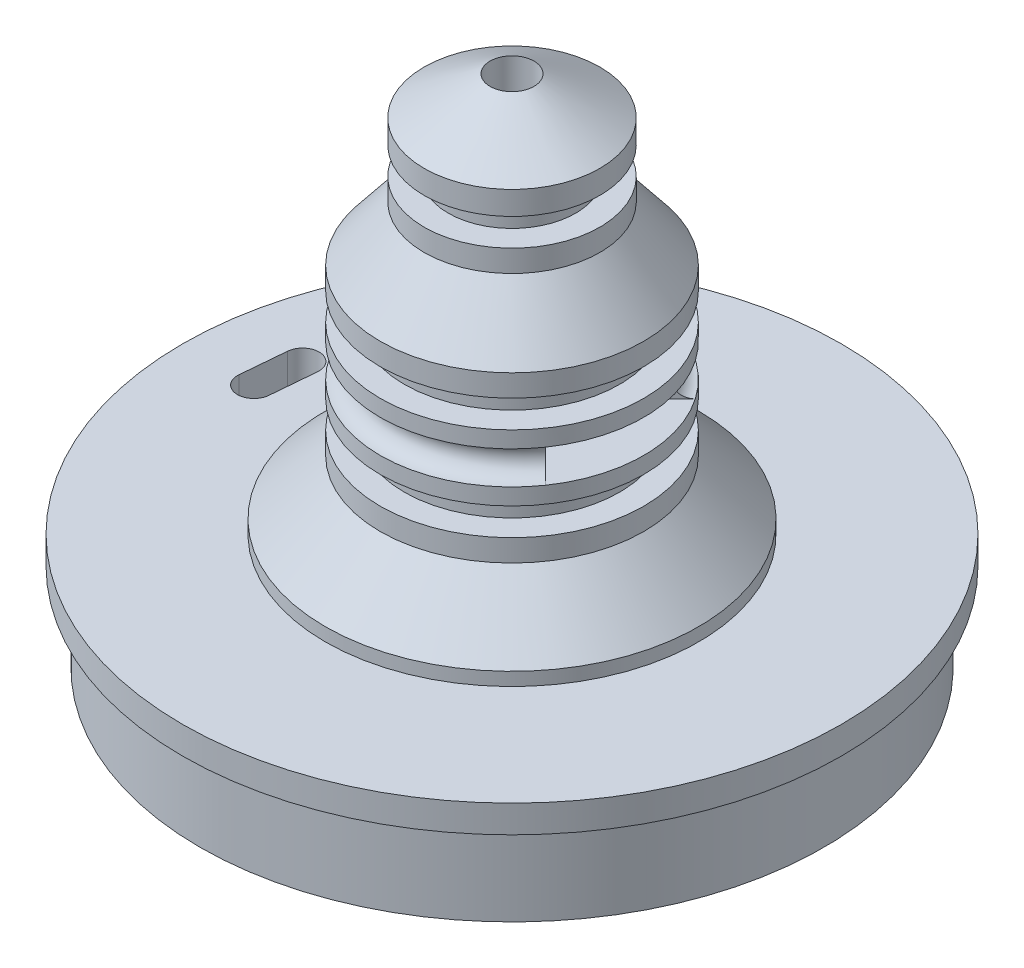
SolidWorks part; units mm, degrees
ref_plane "Спереди" through (0, 0, 0) normal (0, 0, 1) x (1, 0, 0)
ref_plane "Сверху" through (0, 0, 0) normal (0, 1, 0) x (1, 0, 0)
ref_plane "Справа" through (0, 0, 0) normal (1, 0, 0) x (0, 0, -1)
sketch "Эскиз1" plane through (0, 0, 0) normal (0, 0, 1) x (1, 0, 0)
  line L0 (0, 0) -> (0, 60) construction
  line L1 (17, 27) -> (17, 25.8)
  line L2 (2, 62.0979) -> (2, 15.3)
  line L6 (8, 56.5) -> (5.8, 56.5)
  line L7 (5.8, 56.5) -> (5.8, 54)
  line L8 (5.8, 54) -> (8, 54)
  line L10 (8, 58.6338) -> (8, 56.5)
  line L11 (8, 54) -> (8, 52)
  line L12 (8, 52) -> (12, 47)
  line L13 (12, 47) -> (12, 45)
  line L14 (12, 45) -> (9.8, 45)
  line L15 (9.8, 45) -> (9.8, 42.5)
  line L16 (9.8, 42.5) -> (12, 42.5)
  line L17 (12, 39.5) -> (9.0242, 39.5) construction
  line L18 (12, 42.5) -> (12, 41)
  line L19 (12, 36.5) -> (12, 38)
  line L20 (12, 34) -> (9.8, 34)
  line L21 (9.8, 34) -> (9.8, 36.5)
  line L22 (9.8, 36.5) -> (12, 36.5)
  line L23 (12, 34) -> (12, 32)
  line L24 (12, 32) -> (17, 27)
  line L29 (17, 25.8) -> (30, 25.8)
  line L33 (30, 25.8) -> (30, 23.3)
  line L34 (30, 23.3) -> (28.4, 23.3)
  line L35 (28.4, 23.3) -> (28.4, 15.3)
  line L36 (28.4, 15.3) -> (2, 15.3)
  line L37 (8, 58.6338) -> (2, 62.0979)
  arc A1 (12, 41) -> (12, 38) centre (12, 39.5) ccw
  point P22 (12, 41)
  dimension "D5" = 2.5
  dimension "D14" = 3
  dimension "D3" = 4
  dimension "D4" = 16
  dimension "D6" = 2
  dimension "D7" = 2.2
  dimension "D8" = 60
  dimension "D9" = 24
  dimension "D10" = 5
  dimension "D11" = 2.5
  dimension "D12" = 2.2
  dimension "D13" = 2
  dimension "D15" = 1.5
  dimension "D16" = 2
  dimension "D17" = 5
  dimension "D18" = 34
  dimension "D19" = 1.2
  dimension "D20" = 2.5
  dimension "D21" = 8
  dimension "D22" = 13
  dimension "D23" = 1.6
  dimension "D24" = 7.8
revolve "Повернуть1" add sketch "Эскиз1" angle 360 about L0 reverse direction yes
sketch "Эскиз3" plane through (0, 15.3, 0) normal (0, -1, 0) x (1, 0, 0)
  line L0 (50, 0) -> (-50, 0) construction
  circle A0 centre (5.9, 0) radius 2
  dimension "D1" = 4
  dimension "D2" = 5.9
ref_plane "Плоскость1" through (0, 41, 0) normal (0, -1, 0) x (-1, 0, 0)
extrude "Вырез-Вытянуть1" cut sketch "Эскиз3" against normal up to surface (25.7 mm away) up to plane "Плоскость1"
ref_plane "Плоскость2" through (0, 38, 0) normal (0, -1, 0) x (-1, 0, 0)
sketch "Эскиз4" plane through (0, 41, 0) normal (0, -1, 0) x (-1, 0, 0)
  line L0 (-4.4858, 1.4142) -> (-9.8809, 6.8094)
  line L1 (-5.9, 0) -> (-22.1819, 0) construction
  line L2 (-50, 0) -> (50, 0) construction
  line L3 (-4.4858, -1.4142) -> (-9.8809, -6.8094)
  circle A0 centre (0, 0) radius 12 construction
  arc A1 (-9.8809, 6.8094) -> (-9.8809, -6.8094) centre (0, 0) ccw
  circle A2 centre (-5.9, 0) radius 2 construction
  arc A3 (-4.4858, -1.4142) -> (-4.4858, 1.4142) centre (-5.9, 0) ccw
  dimension "D1" = 90
extrude "Вырез-Вытянуть2" cut sketch "Эскиз4" along normal up to surface (3 mm away) up to plane "Плоскость2"
extrude "Вырез-Вытянуть3" cut sketch "Эскиз5" against normal blind 10.5 contours L2 A7 L1 A1 A5 A3 region at (-23.3215, 15.3, -2.0404) body kept at (17, 27, 0)
sketch "Эскиз5" plane through (0, 15.3, 0) normal (0, -1, 0) x (1, 0, 0)
  line L0 (-23.143, -4.0807) -> (-23.5, 0) construction
  line L1 (-24.6373, -4.2115) -> (-24.9943, -0.1307)
  line L2 (-21.6487, -3.95) -> (-22.0057, 0.1307)
  arc A1 (-24.6373, -4.2115) -> (-21.6487, -3.95) centre (-23.143, -4.0807) ccw
  circle A3 centre (-23.5, 0) radius 0.5
  circle A5 centre (-23.143, -4.0807) radius 0.5
  circle A6 centre (-23.5, 0) radius 0.5
  arc A7 (-22.0057, 0.1307) -> (-24.9943, -0.1307) centre (-23.5, 0) ccw
  point P2 (-23.3215, -2.0404)
